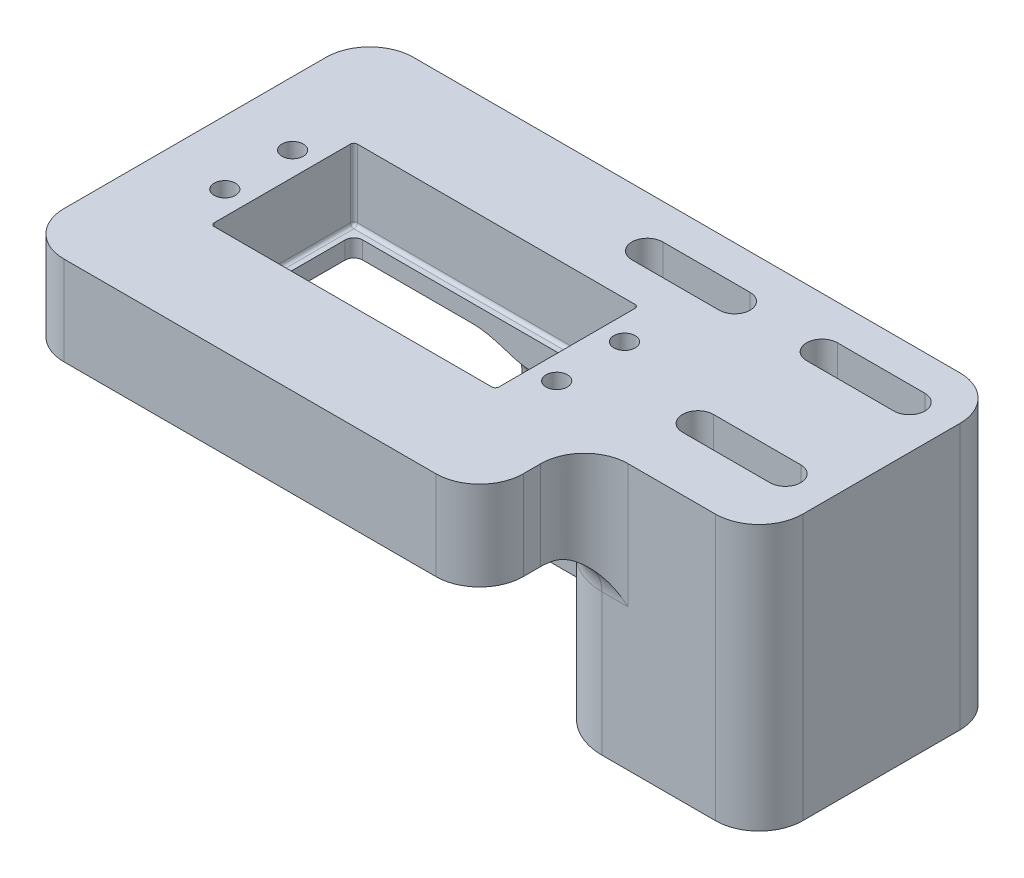
SolidWorks part; units mm, degrees
ref_plane "Front Plane" through (0, 0, 0) normal (0, 0, 1) x (1, 0, 0)
ref_plane "Top Plane" through (0, 0, 0) normal (0, 1, 0) x (1, 0, 0)
ref_plane "Right Plane" through (0, 0, 0) normal (1, 0, 0) x (0, 0, -1)
sketch "Sketch1" plane through (0, 0, 0) normal (0, 1, 0) x (1, 0, 0)
  line L1 (-20.6883, -10.4013) -> (20.6883, -10.4013)
  line L2 (-20.6883, -10.4013) -> (-20.6883, 10.4013)
  line L3 (-20.6883, 10.4013) -> (20.6883, 10.4013)
  line L4 (20.6883, -10.4013) -> (20.6883, 10.4013)
  line L5 (0, 10.4013) -> (0, -10.4013) construction
  line L6 (-20.6883, 0) -> (20.6883, 0) construction
  line L7 (-20.0533, 10.0203) -> (20.0533, 10.0203) construction
  line L8 (-20.0533, 10.0203) -> (-20.0533, -10.0203) construction
  line L9 (-20.0533, -10.0203) -> (20.0533, -10.0203) construction
  line L10 (20.0533, 10.0203) -> (20.0533, -10.0203) construction
  line L11 (33.3883, -25.4) -> (-33.3883, -25.4)
  line L12 (33.3883, -25.4) -> (33.3883, 25.4)
  line L13 (33.3883, 25.4) -> (-33.3883, 25.4)
  line L14 (-33.3883, -25.4) -> (-33.3883, 25.4)
  line L15 (0, 25.4) -> (0, -25.4) construction
  line L16 (33.3883, 0) -> (-33.3883, 0) construction
  circle A0 centre (-24.13, 4.9276) radius 2.2606 construction
  circle A1 centre (-24.13, -4.9276) radius 2.2606 construction
  circle A2 centre (24.13, -4.9276) radius 2.2606 construction
  circle A3 centre (24.13, 4.9276) radius 2.2606 construction
  circle A12 centre (-24.13, 4.9276) radius 2.0955
  circle A13 centre (-24.13, -4.9276) radius 2.0955
  circle A14 centre (24.13, -4.9276) radius 2.0955
  circle A15 centre (24.13, 4.9276) radius 2.0955
  point P0 (0, 0)
  point P8 (0, -10.0203)
  point P9 (-20.0533, 0)
  point P18 (0, 0)
  dimension "D5" = 4.5212
  dimension "D8" = 4.191
  dimension "D1" = 40.1066
  dimension "D2" = 20.0406
  dimension "D3" = 9.8552
  dimension "D4" = 48.26
  dimension "D6" = 0.635
  dimension "D7" = 0.381
  dimension "D9" = 12.7
  dimension "D10" = 50.8
extrude "Boss-Extrude1" add sketch "Sketch1" against normal blind 10.414
sketch "Sketch4" plane through (0, 0, 0) normal (0, 1, 0) x (1, 0, 0)
  line L1 (33.3883, 25.4) -> (58.7883, 25.4)
  line L2 (33.3883, 25.4) -> (33.3883, -10.16)
  line L3 (33.3883, -10.16) -> (58.7883, -10.16)
  line L4 (58.7883, 25.4) -> (58.7883, -10.16)
  dimension "D1" = 25.4
  dimension "D2" = 35.56
extrude "Boss-Extrude4" add sketch "Sketch4" against normal blind 38.608
sketch "Sketch5" plane through (0, -10.414, 0) normal (0, -1, 0) x (1, 0, 0)
  line L0 (33.3883, -25.4) -> (-33.3883, -25.4) construction
  line L1 (33.3883, 10.16) -> (27.0383, 10.16)
  line L2 (33.3883, 10.16) -> (33.3883, -25.4)
  line L4 (27.0383, 10.16) -> (27.0383, -10.4013)
  line L5 (20.6883, -10.4013) -> (-20.6883, -10.4013) construction
  line L6 (0, -10.4013) -> (27.0383, -10.4013)
  line L7 (0, -10.4013) -> (0, -25.4)
  line L8 (0, -25.4) -> (33.3883, -25.4)
  dimension "D1" = 6.35
extrude "Boss-Extrude5" add sketch "Sketch5" along normal up to surface (28.194 mm away) up to face at (46.0883, -38.608, -7.62)
sketch "Sketch6" plane through (0, 0, 0) normal (0, 1, 0) x (1, 0, 0)
  line L0 (39.7383, 0) -> (52.4383, 0) construction
  line L1 (39.7383, 2.2479) -> (52.4383, 2.2479)
  line L2 (39.7383, -2.2479) -> (52.4383, -2.2479)
  line L3 (20.6883, -10.4013) -> (20.6883, 10.4013) construction
  line L4 (39.7383, 18.034) -> (52.4383, 18.034) construction
  line L5 (39.7383, 20.2819) -> (52.4383, 20.2819)
  line L6 (39.7383, 15.7861) -> (52.4383, 15.7861)
  line L7 (33.3883, 25.4) -> (33.3883, 18.034) construction
  line L8 (58.7883, 25.4) -> (-33.3883, 25.4) construction
  line L9 (27.0383, 18.034) -> (14.3383, 18.034) construction
  line L10 (27.0383, 20.2819) -> (14.3383, 20.2819)
  line L11 (27.0383, 15.7861) -> (14.3383, 15.7861)
  arc A0 (39.7383, 2.2479) -> (39.7383, -2.2479) centre (39.7383, 0) ccw
  arc A1 (52.4383, -2.2479) -> (52.4383, 2.2479) centre (52.4383, 0) ccw
  arc A2 (39.7383, 20.2819) -> (39.7383, 15.7861) centre (39.7383, 18.034) ccw
  arc A3 (52.4383, 15.7861) -> (52.4383, 20.2819) centre (52.4383, 18.034) ccw
  arc A4 (27.0383, 20.2819) -> (27.0383, 15.7861) centre (27.0383, 18.034) cw
  arc A5 (14.3383, 15.7861) -> (14.3383, 20.2819) centre (14.3383, 18.034) cw
  point P2 (46.0883, 0)
  point P12 (46.0883, 18.034)
  point P19 (20.6883, 18.034)
  dimension "D1" = 25.4
  dimension "D2" = 4.4958
  dimension "D3" = 18.034
  dimension "D4" = 12.7
  dimension "D6" = 25.4
extrude "Cut-Extrude1" cut sketch "Sketch6" against normal through all
fillet "Fillet1" radius 6.35 9 edges at (0, -24.511, -25.4) (0, -24.511, -10.4013) (27.0383, -24.511, -10.4013) (-33.3883, -5.207, -25.4) (-33.3883, -5.207, 25.4) (33.3883, -5.207, 25.4) (58.7883, -19.304, -25.4) (58.7883, -19.304, 10.16) (33.3883, -5.207, 10.16)
fillet "Fillet2" radius 8.89 1 edges at (27.0383, -24.511, 10.16)
sketch "Sketch7" plane through (0, -10.414, 0) normal (0, -1, 0) x (1, 0, 0)
  line L0 (0, 10.4013) -> (0, -10.4013) construction
  line L1 (-24.13, 8.1538) -> (-26.924, 6.5407)
  line L2 (-26.924, 6.5407) -> (-26.924, 3.3145)
  line L3 (-26.924, 3.3145) -> (-24.13, 1.7014)
  line L4 (-24.13, 1.7014) -> (-21.336, 3.3145)
  line L5 (-21.336, 3.3145) -> (-21.336, 6.5407)
  line L6 (-21.336, 6.5407) -> (-24.13, 8.1538)
  line L7 (-20.6883, 10.4013) -> (20.6883, 10.4013) construction
  line L8 (6.35, -10.4013) -> (-20.6883, -10.4013) construction
  line L9 (-20.6883, 0) -> (20.6883, 0) construction
  line L10 (-20.6883, -10.4013) -> (-20.6883, 10.4013) construction
  line L11 (20.6883, 10.4013) -> (20.6883, -10.4013) construction
  line L12 (-21.336, -6.5407) -> (-24.13, -8.1538)
  line L13 (-21.336, -3.3145) -> (-21.336, -6.5407)
  line L14 (-24.13, -1.7014) -> (-21.336, -3.3145)
  line L15 (-26.924, -3.3145) -> (-24.13, -1.7014)
  line L16 (-26.924, -6.5407) -> (-26.924, -3.3145)
  line L17 (-24.13, -8.1538) -> (-26.924, -6.5407)
  line L18 (24.13, -8.1538) -> (26.924, -6.5407)
  line L19 (26.924, -6.5407) -> (26.924, -3.3145)
  line L20 (26.924, -3.3145) -> (24.13, -1.7014)
  line L21 (24.13, -1.7014) -> (21.336, -3.3145)
  line L22 (21.336, -3.3145) -> (21.336, -6.5407)
  line L23 (21.336, -6.5407) -> (24.13, -8.1538)
  line L24 (21.336, 6.5407) -> (24.13, 8.1538)
  line L25 (21.336, 3.3145) -> (21.336, 6.5407)
  line L26 (24.13, 1.7014) -> (21.336, 3.3145)
  line L27 (26.924, 3.3145) -> (24.13, 1.7014)
  line L28 (26.924, 6.5407) -> (26.924, 3.3145)
  line L29 (24.13, 8.1538) -> (26.924, 6.5407)
  circle A0 centre (-24.13, 4.9276) radius 2.794 construction
  circle A1 centre (-24.13, -4.9276) radius 2.794 construction
  circle A2 centre (24.13, -4.9276) radius 2.794 construction
  circle A3 centre (24.13, 4.9276) radius 2.794 construction
  dimension "D1" = 5.588
extrude "Cut-Extrude2" cut sketch "Sketch7" along normal through all
sketch "Sketch8" plane through (0, -10.414, 0) normal (0, -1, 0) x (1, 0, 0)
  line L0 (6.35, -10.4013) -> (20.6883, -10.4013)
  line L1 (-20.6883, 10.4013) -> (20.6883, 10.4013) construction
  line L2 (-19.4183, 9.1313) -> (19.4183, 9.1313)
  line L3 (-19.4183, 9.1313) -> (-19.4183, -9.1313)
  line L4 (-19.4183, -9.1313) -> (19.4183, -9.1313)
  line L5 (19.4183, 9.1313) -> (19.4183, -9.1313)
  line L6 (-24.13, 8.1538) -> (-26.924, 6.5407)
  line L7 (-26.924, 6.5407) -> (-26.924, 3.3145)
  line L8 (-26.924, 3.3145) -> (-24.13, 1.7014)
  line L9 (-24.13, 1.7014) -> (-21.336, 3.3145)
  line L10 (-21.336, 3.3145) -> (-21.336, 6.5407)
  line L11 (-21.336, 6.5407) -> (-24.13, 8.1538)
  line L12 (-24.13, 8.1538) -> (-26.924, 6.5407)
  line L13 (-26.924, 6.5407) -> (-26.924, 3.3145)
  line L14 (-26.924, 3.3145) -> (-24.13, 1.7014)
  line L15 (-24.13, 1.7014) -> (-21.336, 3.3145)
  line L16 (-21.336, 3.3145) -> (-21.336, 6.5407)
  line L17 (-21.336, 6.5407) -> (-24.13, 8.1538)
  line L18 (-24.13, -8.1538) -> (-21.336, -6.5407)
  line L19 (-26.924, -6.5407) -> (-24.13, -8.1538)
  line L20 (-26.924, -3.3145) -> (-26.924, -6.5407)
  line L21 (-24.13, -1.7014) -> (-26.924, -3.3145)
  line L22 (-21.336, -3.3145) -> (-24.13, -1.7014)
  line L23 (-21.336, -6.5407) -> (-21.336, -3.3145)
  line L24 (-24.13, -8.1538) -> (-21.336, -6.5407)
  line L25 (-26.924, -6.5407) -> (-24.13, -8.1538)
  line L26 (-26.924, -3.3145) -> (-26.924, -6.5407)
  line L27 (-24.13, -1.7014) -> (-26.924, -3.3145)
  line L28 (-21.336, -3.3145) -> (-24.13, -1.7014)
  line L29 (-21.336, -6.5407) -> (-21.336, -3.3145)
  line L30 (24.13, 8.1538) -> (21.336, 6.5407)
  line L31 (26.924, 6.5407) -> (24.13, 8.1538)
  line L32 (26.924, 3.3145) -> (26.924, 6.5407)
  line L33 (24.13, 1.7014) -> (26.924, 3.3145)
  line L34 (21.336, 3.3145) -> (24.13, 1.7014)
  line L35 (21.336, 6.5407) -> (21.336, 3.3145)
  line L36 (24.13, 8.1538) -> (21.336, 6.5407)
  line L37 (26.924, 6.5407) -> (24.13, 8.1538)
  line L38 (26.924, 3.3145) -> (26.924, 6.5407)
  line L39 (24.13, 1.7014) -> (26.924, 3.3145)
  line L40 (21.336, 3.3145) -> (24.13, 1.7014)
  line L41 (21.336, 6.5407) -> (21.336, 3.3145)
  line L42 (24.13, -8.1538) -> (26.924, -6.5407)
  line L43 (26.924, -6.5407) -> (26.924, -3.3145)
  line L44 (26.924, -3.3145) -> (24.13, -1.7014)
  line L45 (24.13, -1.7014) -> (21.336, -3.3145)
  line L46 (21.336, -3.3145) -> (21.336, -6.5407)
  line L47 (21.336, -6.5407) -> (24.13, -8.1538)
  line L48 (24.13, -8.1538) -> (26.3883, -6.85)
  line L49 (26.924, -5.2507) -> (26.924, -3.3145)
  line L50 (26.924, -3.3145) -> (24.13, -1.7014)
  line L51 (24.13, -1.7014) -> (21.336, -3.3145)
  line L52 (21.336, -3.3145) -> (21.336, -6.5407)
  line L53 (21.336, -6.5407) -> (24.13, -8.1538)
  line L54 (0, 9.1313) -> (0, 10.4013) construction
  line L55 (-19.4183, 0) -> (-20.6883, 0) construction
  line L56 (-20.6883, -10.4013) -> (-20.6883, 10.4013) construction
  line L57 (0, -9.1313) -> (0, -10.4013) construction
  line L58 (19.4183, 0) -> (20.6883, 0) construction
  line L59 (20.6883, 10.4013) -> (20.6883, -10.4013) construction
  line L61 (26.3883, -6.85) -> (26.924, -6.5407)
  line L62 (26.924, -6.5407) -> (26.924, -5.2507)
  line L63 (27.0383, -4.0513) -> (27.0383, 1.27)
  line L64 (35.9283, 10.16) -> (39.7383, 10.16)
  line L65 (33.3883, 16.51) -> (33.3883, 19.05)
  line L66 (27.0383, 25.4) -> (-27.0383, 25.4)
  line L67 (-33.3883, 19.05) -> (-33.3883, -19.05)
  line L68 (-27.0383, -25.4) -> (6.35, -25.4)
  line L69 (0, -19.05) -> (0, -16.7513)
  line L70 (6.35, -10.4013) -> (-20.6883, -10.4013)
  line L71 (-20.6883, -10.4013) -> (-20.6883, 10.4013)
  line L72 (-20.6883, 10.4013) -> (20.6883, 10.4013)
  line L73 (20.6883, 10.4013) -> (20.6883, -10.4013)
  line L76 (27.0383, -4.0513) -> (27.0383, 1.27)
  line L77 (35.9283, 10.16) -> (39.7383, 10.16)
  line L78 (33.3883, 16.51) -> (33.3883, 19.05)
  line L79 (27.0383, 25.4) -> (-27.0383, 25.4)
  line L80 (-33.3883, 19.05) -> (-33.3883, -19.05)
  line L81 (-27.0383, -25.4) -> (6.35, -25.4)
  line L82 (0, -19.05) -> (0, -16.7513)
  line L83 (6.35, -10.4013) -> (0, -10.4013)
  arc A9 (20.6883, -10.4013) -> (26.3883, -6.85) centre (20.6883, -4.0513) ccw
  arc A10 (26.924, -5.2507) -> (27.0383, -4.0513) centre (20.6883, -4.0513) ccw
  arc A11 (35.9283, 10.16) -> (27.0383, 1.27) centre (35.9283, 1.27) ccw
  arc A12 (33.3883, 16.51) -> (39.7383, 10.16) centre (39.7383, 16.51) ccw
  arc A13 (33.3883, 19.05) -> (27.0383, 25.4) centre (27.0383, 19.05) ccw
  arc A14 (-27.0383, 25.4) -> (-33.3883, 19.05) centre (-27.0383, 19.05) ccw
  arc A15 (-33.3883, -19.05) -> (-27.0383, -25.4) centre (-27.0383, -19.05) ccw
  arc A16 (0, -19.05) -> (6.35, -25.4) centre (6.35, -19.05) ccw
  arc A17 (6.35, -10.4013) -> (0, -16.7513) centre (6.35, -16.7513) ccw
  arc A18 (20.6883, -10.4013) -> (26.3883, -6.85) centre (20.6883, -4.0513) ccw
  arc A19 (26.924, -5.2507) -> (27.0383, -4.0513) centre (20.6883, -4.0513) ccw
  arc A21 (33.3883, 16.51) -> (39.7383, 10.16) centre (39.7383, 16.51) ccw
  arc A22 (33.3883, 19.05) -> (27.0383, 25.4) centre (27.0383, 19.05) ccw
  arc A23 (-27.0383, 25.4) -> (-33.3883, 19.05) centre (-27.0383, 19.05) ccw
  arc A24 (-33.3883, -19.05) -> (-27.0383, -25.4) centre (-27.0383, -19.05) ccw
  arc A25 (0, -19.05) -> (6.35, -25.4) centre (6.35, -19.05) ccw
  arc A26 (6.35, -10.4013) -> (0, -16.7513) centre (6.35, -16.7513) ccw
  arc A27 (35.9283, 10.16) -> (27.0383, 1.27) centre (35.9283, 1.27) ccw
  arc M52 (20.6883, -10.4013) -> (26.3883, -6.85) centre (20.6883, -4.0513) ccw
  arc M55 (26.924, -5.2507) -> (27.0383, -4.0513) centre (20.6883, -4.0513) ccw
  line M56 (27.0383, -4.0513) -> (27.0383, 1.27)
  line M58 (35.9283, 10.16) -> (39.7383, 10.16)
  arc M59 (39.7383, 10.16) -> (33.3883, 16.51) centre (39.7383, 16.51) cw
  line M60 (33.3883, 16.51) -> (33.3883, 19.05)
  arc M61 (33.3883, 19.05) -> (27.0383, 25.4) centre (27.0383, 19.05) ccw
  line M62 (27.0383, 25.4) -> (-27.0383, 25.4)
  arc M63 (-27.0383, 25.4) -> (-33.3883, 19.05) centre (-27.0383, 19.05) ccw
  line M64 (-33.3883, 19.05) -> (-33.3883, -19.05)
  arc M65 (-33.3883, -19.05) -> (-27.0383, -25.4) centre (-27.0383, -19.05) ccw
  line M66 (-27.0383, -25.4) -> (6.35, -25.4)
  arc M67 (6.35, -25.4) -> (0, -19.05) centre (6.35, -19.05) cw
  line M68 (0, -19.05) -> (0, -16.7513)
  arc M69 (0, -16.7513) -> (6.35, -10.4013) centre (6.35, -16.7513) cw
  line M70 (6.35, -10.4013) -> (-20.6883, -10.4013)
  line M71 (-20.6883, -10.4013) -> (-20.6883, 10.4013)
  line M72 (-20.6883, 10.4013) -> (20.6883, 10.4013)
  line M73 (20.6883, 10.4013) -> (20.6883, -10.4013)
  dimension "D6" = 1.27
  dimension "D1" = 0
  dimension "D2" = 0
  dimension "D3" = 0
  dimension "D4" = 0
  dimension "D5" = 0
extrude "Boss-Extrude6" add sketch "Sketch8" along normal blind 2.54 contours L53 L52 L51 L50 L49 L48 L41 L36 L37 L38 L39 L40 L29 L24 L25 L26 L27 L28 L17 L16 L15 L14 L13 L12 M55 M56 M58 M59 M60 M61 M62 M63 M64 M65 M66 M67 M68 M69 M70 M71 M72 M73 M52 | L0 L2 L5 L4 L3 M70 M73 M72 M71 region at (3.175, -10.414, -9.9382) region at (1.2303, -10.414, -11.6316)
sketch "Sketch9" plane through (0, 0, 0) normal (0, 1, 0) x (1, 0, 0)
  circle A0 centre (-24.13, -4.9276) radius 2.0955 construction
  circle A1 centre (24.13, -4.9276) radius 2.0955 construction
  circle A2 centre (24.13, 4.9276) radius 2.0955 construction
  circle A3 centre (-24.13, 4.9276) radius 2.0955 construction
  circle A4 centre (-24.13, -4.9276) radius 2.0955
  circle A5 centre (24.13, -4.9276) radius 2.0955
  circle A6 centre (24.13, 4.9276) radius 2.0955
  circle A7 centre (-24.13, 4.9276) radius 2.0955
  circle A8 centre (-24.13, 4.9276) radius 1.55
  circle A9 centre (-24.13, -4.9276) radius 1.55
  circle A10 centre (24.13, -4.9276) radius 1.55
  circle A11 centre (24.13, 4.9276) radius 1.55
  dimension "D1" = 3.1
extrude "Boss-Extrude7" add sketch "Sketch9" against normal up to surface (10.414 mm away) up to face at (-24.13, -10.414, 4.9276)
fillet "Fillet4" radius 1.27 4 edges at (-19.4183, -11.684, -9.1313) (-19.4183, -11.684, 9.1313) (19.4183, -11.684, 9.1313) (19.4183, -11.684, -9.1313)
fillet "Fillet3" radius 5.08 9 edges at (27.0097, -12.954, -4.6537) (37.8333, -12.954, 10.16) (1.8599, -12.954, -23.5401) (0, -12.954, -17.9006) (24.0462, -12.954, -9.4408) (13.5192, -12.954, -10.4013) (27.0383, -12.954, -1.3906) (1.8599, -12.954, -12.2612) (29.6421, -12.954, 7.5562)
fillet "Fillet5" radius 0.508 8 edges at (-20.6883, -10.414, 0) (0, -10.414, 10.4013) (20.6883, -10.414, 0) (0, -10.414, -10.4013) (-20.6883, -5.207, 10.4013) (20.6883, -5.207, 10.4013) (20.6883, -5.207, -10.4013) (-20.6883, -5.207, -10.4013)
